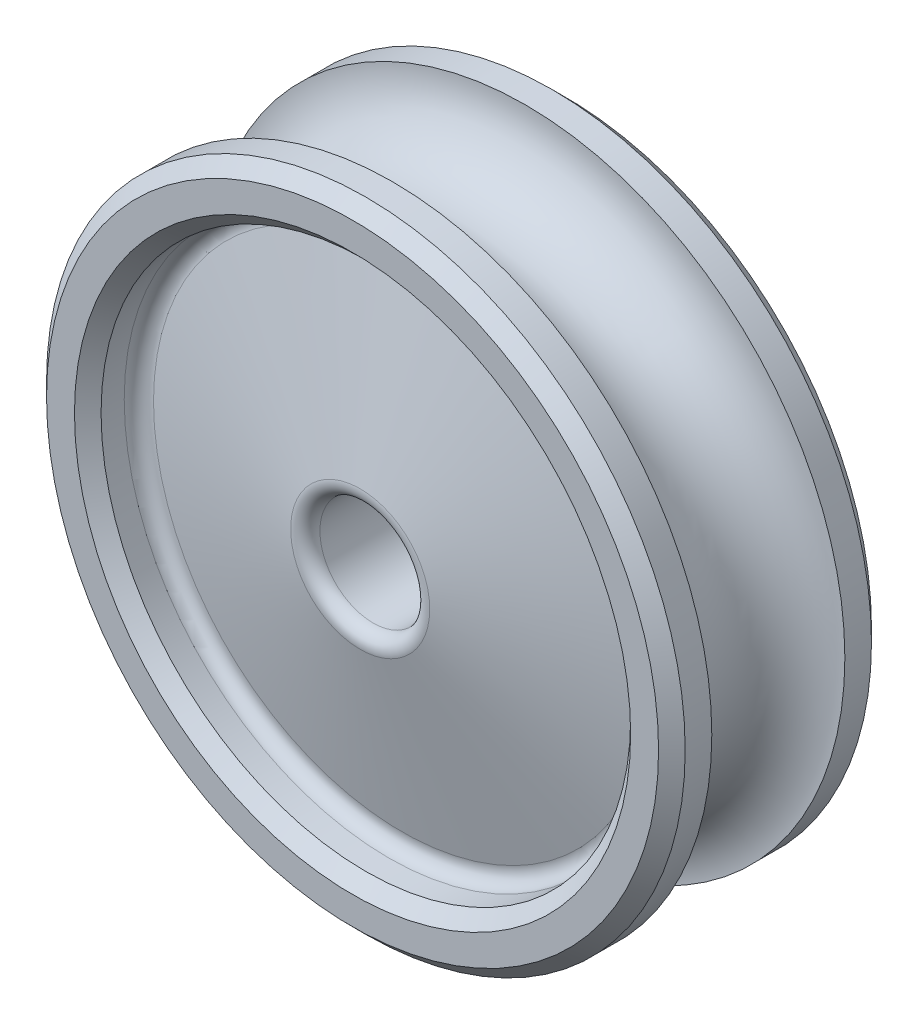
SolidWorks part; units mm, degrees
ref_plane "Front Plane" through (0, 0, 0) normal (0, 0, 1) x (1, 0, 0)
ref_plane "Top Plane" through (0, 0, 0) normal (0, 1, 0) x (1, 0, 0)
ref_plane "Right Plane" through (0, 0, 0) normal (1, 0, 0) x (0, 0, -1)
sketch "Sketch1" plane through (0, 0, 0) normal (0, 0, 1) x (1, 0, 0)
  circle A0 centre (0, 0) radius 152.4
  dimension "D1" = 304.8
extrude "Boss-Extrude1" add sketch "Sketch1" along normal blind 101.6
sketch "Sketch2" plane through (0, 0, 0) normal (1, 0, 0) x (0, 0, -1)
  line L0 (0, 152.4) -> (-101.6, 152.4) construction
  circle A0 centre (-50.8, 152.4) radius 31.75
  dimension "D1" = 63.5
ref_plane "Plane1" through (0, 0, 50.8) normal (0, 0, 1) x (1, 0, 0)
sketch "Sketch3" plane through (0, 0, 50.8) normal (0, 0, 1) x (1, 0, 0)
  circle A0 centre (0, 0) radius 152.4
sweep "Cut-Sweep1" cut profiles "Sketch2" path "Sketch3"
sketch "Sketch4" plane through (0, 0, 101.6) normal (0, 0, 1) x (1, 0, 0)
  circle A0 centre (0, 0) radius 25.4
  dimension "D1" = 50.8
extrude "Cut-Extrude1" cut sketch "Sketch4" against normal through all
sketch "Sketch6" plane through (0, 0, 0) normal (1, 0, 0) x (0, 0, -1)
  line L0 (-25.4, 126.3693) -> (0, 126.3693)
  line L1 (0, -152.4) -> (0, 152.4) construction
  line L2 (0, 126.3693) -> (0, 17.5809)
  line L3 (0, 17.5809) -> (-25.4, 126.3693)
  line L4 (3.2562, 0) -> (0, 0) construction
  line L5 (0, 0) -> (-83.1538, 0) construction
  dimension "D1" = 25.4
revolve "Cut-Revolve5" cut sketch "Sketch6" angle 360 about L5
mirror "Mirror1" about plane through (0, 0, 50.8) normal (0, 0, 1) of "Cut-Revolve5"
chamfer "Chamfer1" distance 6.35 angle 45 4 edges at (-126.3693, 0, 0) (152.4, 0, 0) (-126.3693, 0, 101.6) (152.4, 0, 101.6)
fillet "Fillet1" radius 6.35 1 edges at (-126.3693, 0, 76.2)
fillet "Fillet2" radius 6.35 1 edges at (-126.3693, 0, 25.4)
fillet "Fillet3" radius 6.35 2 edges at (-25.4, 0, 99.7744) (25.4, 0, 1.8256)
